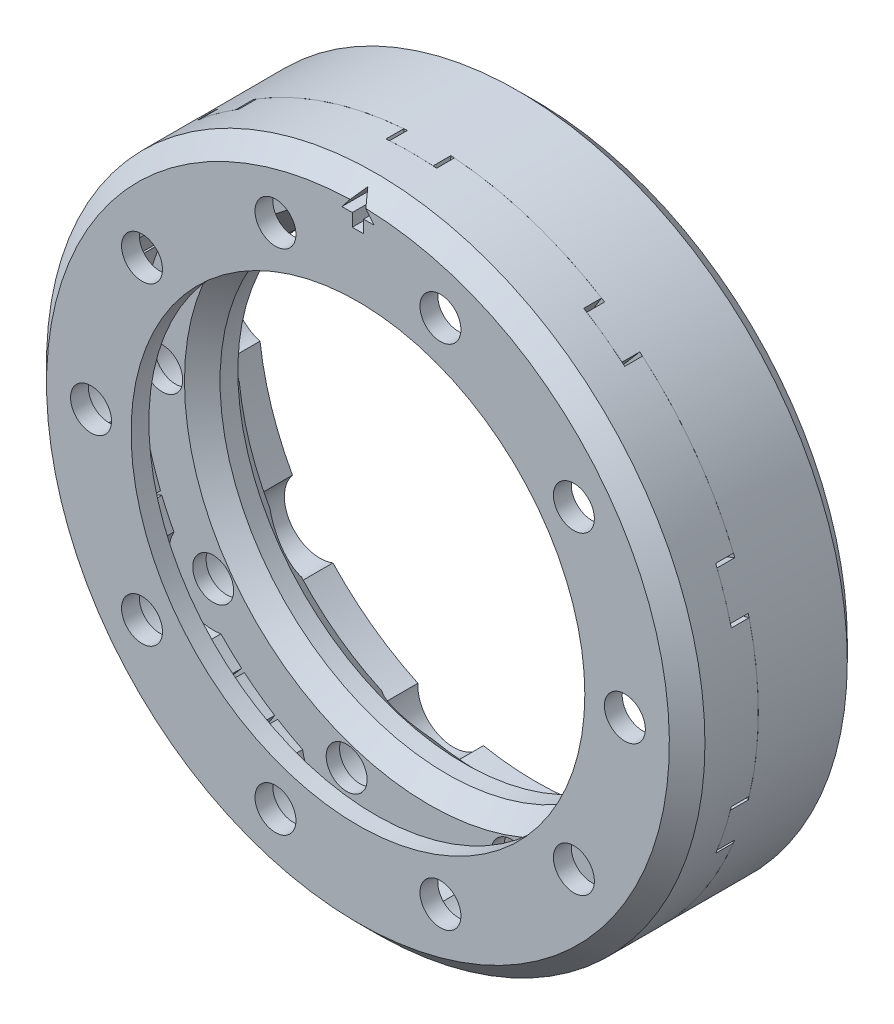
SolidWorks part; units mm, degrees
ref_plane "Front Plane" through (0, 0, 0) normal (0, 0, 1) x (1, 0, 0)
ref_plane "Top Plane" through (0, 0, 0) normal (0, 1, 0) x (1, 0, 0)
ref_plane "Right Plane" through (0, 0, 0) normal (1, 0, 0) x (0, 0, -1)
curve "Curve1"
  spline degree 3 poles (24.0017, -0.2353, 0) (23.9991, 0, 0) (24.0017, 0.2353, 0) (24.0094, 0.4695, 0) (24.022, 0.7014, 0) (24.0393, 0.9301, 0) (24.0607, 1.1546, 0) (24.0858, 1.3743, 0) (24.1142, 1.5885, 0) (24.1451, 1.7968, 0) (24.1782, 1.999, 0) (24.2129, 2.1951, 0) (24.2487, 2.385, 0) (24.2853, 2.5689, 0) (24.3221, 2.747, 0) (24.359, 2.9198, 0) (24.3955, 3.0875, 0) (24.4316, 3.2505, 0) (24.4669, 3.4093, 0) (24.5014, 3.5643, 0) (24.5349, 3.716, 0) (24.5673, 3.8647, 0) (24.5985, 4.0109, 0) (24.6284, 4.1549, 0) (24.6569, 4.2972, 0) (24.6841, 4.438, 0) (24.7098, 4.5776, 0) (24.7339, 4.7164, 0) (24.7564, 4.8545, 0) (24.7773, 4.9923, 0) (24.7964, 5.1299, 0) (24.8137, 5.2675, 0) (24.8292, 5.4052, 0) (24.8427, 5.5433, 0) (24.8542, 5.6817, 0) (24.8635, 5.8205, 0) (24.8707, 5.96, 0) (24.8756, 6.1, 0) (24.8782, 6.2406, 0) (24.8784, 6.3818, 0) (24.8761, 6.5236, 0) (24.8712, 6.666, 0) (24.8637, 6.809, 0) (24.8535, 6.9524, 0) (24.8406, 7.0963, 0) (24.8248, 7.2405, 0) (24.8062, 7.385, 0) (24.7847, 7.5297, 0) (24.7603, 7.6745, 0) (24.7329, 7.8193, 0) (24.7025, 7.964, 0) (24.6691, 8.1084, 0) (24.6328, 8.2524, 0) (24.5934, 8.3959, 0) (24.5511, 8.5389, 0) (24.5059, 8.6811, 0) (24.4577, 8.8224, 0) (24.4066, 8.9627, 0) (24.3527, 9.102, 0) (24.2959, 9.24, 0) (24.2365, 9.3767, 0) (24.1743, 9.5119, 0) (24.1096, 9.6457, 0) (24.0423, 9.7777, 0) (23.9726, 9.908, 0) (23.9006, 10.0365, 0) (23.8262, 10.1632, 0) (23.7497, 10.2878, 0) (23.671, 10.4105, 0) (23.5904, 10.5311, 0) (23.5078, 10.6497, 0) (23.4234, 10.7661, 0) (23.3373, 10.8805, 0) (23.2495, 10.9927, 0) (23.1601, 11.1028, 0) (23.0692, 11.2109, 0) (22.9768, 11.3169, 0) (22.8831, 11.421, 0) (22.7879, 11.5232, 0) (22.6915, 11.6235, 0) (22.5937, 11.7222, 0) (22.4947, 11.8192, 0) (22.3943, 11.9148, 0) (22.2926, 12.0091, 0) (22.1895, 12.1022, 0) (22.0849, 12.1943, 0) (21.9789, 12.2857, 0) (21.8712, 12.3765, 0) (21.7618, 12.4669, 0) (21.6505, 12.5573, 0) (21.5372, 12.6479, 0) (21.4217, 12.739, 0) (21.3038, 12.831, 0) (21.1834, 12.9241, 0) (21.0603, 13.0188, 0) (20.9342, 13.1153, 0) (20.8051, 13.2143, 0) (20.6726, 13.316, 0) (20.5368, 13.421, 0) (20.3976, 13.5296, 0) (20.2548, 13.6424, 0) (20.1086, 13.7598, 0) (19.9591, 13.8822, 0) (19.8065, 14.0101, 0) (19.6512, 14.1438, 0) (19.4936, 14.2834, 0) (19.3342, 14.4293, 0) (19.1738, 14.5814, 0) (19.013, 14.7396, 0) (18.8528, 14.9037, 0) (18.6941, 15.0733, 0) (18.5377, 15.2477, 0) (18.3844, 15.4263, 0) (18.2351, 15.6083, 0) (18.0905, 15.7926, 0) (17.9511, 15.9784, 0) (17.8173, 16.1647, 0) (17.6894, 16.3504, 0) (17.5674, 16.5348, 0) (17.4515, 16.7171, 0) (17.3413, 16.8966, 0) (17.2366, 17.0728, 0) (17.1372, 17.2453, 0) (17.0426, 17.4138, 0) (16.9524, 17.5781, 0) (16.8661, 17.7383, 0) (16.7833, 17.8943, 0) (16.7035, 18.0463, 0) (16.6263, 18.1943, 0) (16.5513, 18.3387, 0) (16.4781, 18.4796, 0) (16.4062, 18.6174, 0) (16.3354, 18.7521, 0) (16.2653, 18.8841, 0) (16.1957, 19.0137, 0) (16.1261, 19.141, 0) (16.0564, 19.2663, 0) (15.9863, 19.3898, 0) (15.9156, 19.5116, 0) (15.8441, 19.6319, 0) (15.7715, 19.7508, 0) (15.6977, 19.8685, 0) (15.6225, 19.9851, 0) (15.5458, 20.1005, 0) (15.4675, 20.2149, 0) (15.3873, 20.3284, 0) (15.3052, 20.4408, 0) (15.2211, 20.5522, 0) (15.1349, 20.6626, 0) (15.0465, 20.772, 0) (14.9558, 20.8803, 0) (14.8629, 20.9874, 0) (14.7676, 21.0934, 0) (14.67, 21.1981, 0) (14.57, 21.3014, 0) (14.4676, 21.4033, 0) (14.3628, 21.5036, 0) (14.2556, 21.6024, 0) (14.1461, 21.6994, 0) (14.0344, 21.7946, 0) (13.9203, 21.8879, 0) (13.8041, 21.9792, 0) (13.6857, 22.0684, 0) (13.5653, 22.1553, 0) (13.4429, 22.24, 0) (13.3186, 22.3223, 0) (13.1925, 22.4021, 0) (13.0647, 22.4794, 0) (12.9354, 22.5541, 0) (12.8046, 22.6261, 0) (12.6724, 22.6954, 0) (12.539, 22.7619, 0) (12.4045, 22.8255, 0) (12.2689, 22.8864, 0) (12.1325, 22.9443, 0) (11.9953, 22.9993, 0) (11.8575, 23.0514, 0) (11.7192, 23.1006, 0) (11.5804, 23.1469, 0) (11.4413, 23.1904, 0) (11.302, 23.2309, 0) (11.1625, 23.2687, 0) (11.023, 23.3036, 0) (10.8836, 23.3358, 0) (10.7442, 23.3654, 0) (10.6049, 23.3923, 0) (10.4658, 23.4166, 0) (10.3269, 23.4385, 0) (10.1882, 23.4579, 0) (10.0496, 23.4751, 0) (9.9112, 23.49, 0) (9.7729, 23.5027, 0) (9.6347, 23.5134, 0) (9.4963, 23.5221, 0) (9.3578, 23.5289, 0) (9.219, 23.5339, 0) (9.0797, 23.5373, 0) (8.9397, 23.5391, 0) (8.7989, 23.5395, 0) (8.6569, 23.5384, 0) (8.5135, 23.5361, 0) (8.3685, 23.5327, 0) (8.2215, 23.5283, 0) (8.0721, 23.5229, 0) (7.92, 23.5169, 0) (7.7648, 23.5102, 0) (7.6062, 23.5032, 0) (7.4436, 23.496, 0) (7.2768, 23.4888, 0) (7.1053, 23.4819, 0) (6.9288, 23.4756, 0) (6.7469, 23.4702, 0) (6.5595, 23.4662, 0) (6.3662, 23.4639, 0) (6.1672, 23.4638, 0) (5.9623, 23.4663, 0) (5.7517, 23.472, 0) (5.5359, 23.4813, 0) (5.3152, 23.4947, 0) (5.0904, 23.5126, 0) (4.8622, 23.5353, 0) (4.6316, 23.5631, 0) (4.3996, 23.5962, 0) (4.1674, 23.6345, 0) (3.9361, 23.6779, 0) (3.7068, 23.7262, 0) (3.4806, 23.7789, 0) (3.2584, 23.8356, 0) (3.041, 23.8957, 0) (2.829, 23.9585, 0) (2.623, 24.0236, 0) (2.4233, 24.0903, 0) (2.2298, 24.158, 0) (2.0428, 24.2262, 0) (1.862, 24.2945, 0) (1.6873, 24.3624, 0) (1.5182, 24.4296, 0) (1.3545, 24.4959, 0) (1.1957, 24.561, 0) (1.0414, 24.6249, 0) (0.8911, 24.6872, 0) (0.7444, 24.7481, 0) (0.6009, 24.8074, 0) (0.4601, 24.8651, 0) (0.3215, 24.9212, 0) (0.1848, 24.9757, 0) (0.0497, 25.0285, 0) (-0.0842, 25.0797, 0) (-0.2173, 25.1292, 0) (-0.3497, 25.1771, 0) (-0.4819, 25.2233, 0) (-0.6139, 25.2678, 0) (-0.7461, 25.3105, 0) (-0.8786, 25.3514, 0) (-1.0116, 25.3906, 0) (-1.1452, 25.4278, 0) (-1.2795, 25.4632, 0) (-1.4146, 25.4965, 0) (-1.5507, 25.5278, 0) (-1.6877, 25.557, 0) (-1.8257, 25.5839, 0) (-1.9647, 25.6086, 0) (-2.1048, 25.631, 0) (-2.2459, 25.6509, 0) (-2.388, 25.6683, 0) (-2.531, 25.6832, 0) (-2.6749, 25.6954, 0) (-2.8197, 25.705, 0) (-2.9653, 25.7117, 0) (-3.1115, 25.7157, 0) (-3.2584, 25.7168, 0) (-3.4057, 25.7149, 0) (-3.5534, 25.7101, 0) (-3.7014, 25.7023, 0) (-3.8496, 25.6916, 0) (-3.9978, 25.6778, 0) (-4.1459, 25.6609, 0) (-4.2938, 25.641, 0) (-4.4413, 25.6181, 0) (-4.5884, 25.5922, 0) (-4.7349, 25.5632, 0) (-4.8807, 25.5313, 0) (-5.0256, 25.4965, 0) (-5.1696, 25.4588, 0) (-5.3125, 25.4183, 0) (-5.4543, 25.375, 0) (-5.5947, 25.3289, 0) (-5.7338, 25.2803, 0) (-5.8714, 25.229, 0) (-6.0075, 25.1753, 0) (-6.1419, 25.1192, 0) (-6.2747, 25.0607, 0) (-6.4058, 25, 0) (-6.5351, 24.9371, 0) (-6.6627, 24.8721, 0) (-6.7884, 24.8051, 0) (-6.9124, 24.7362, 0) (-7.0346, 24.6655, 0) (-7.1551, 24.5929, 0) (-7.2739, 24.5187, 0) (-7.391, 24.4427, 0) (-7.5066, 24.3652, 0) (-7.6207, 24.286, 0) (-7.7335, 24.2053, 0) (-7.8451, 24.1231, 0) (-7.9556, 24.0393, 0) (-8.0652, 23.9539, 0) (-8.1741, 23.8669, 0) (-8.2824, 23.7783, 0) (-8.3906, 23.6881, 0) (-8.4987, 23.596, 0) (-8.607, 23.5021, 0) (-8.7159, 23.4063, 0) (-8.8257, 23.3083, 0) (-8.9367, 23.2082, 0) (-9.0493, 23.1058, 0) (-9.1639, 23.001, 0) (-9.2809, 22.8936, 0) (-9.4008, 22.7836, 0) (-9.524, 22.6709, 0) (-9.6509, 22.5554, 0) (-9.7821, 22.4371, 0) (-9.9179, 22.3161, 0) (-10.0589, 22.1925, 0) (-10.2055, 22.0665, 0) (-10.3579, 21.9385, 0) (-10.5165, 21.8087, 0) (-10.6814, 21.6777, 0) (-10.8527, 21.5461, 0) (-11.0304, 21.4145, 0) (-11.2141, 21.2837, 0) (-11.4036, 21.1544, 0) (-11.5981, 21.0275, 0) (-11.7971, 20.9038, 0) (-11.9996, 20.7839, 0) (-12.2047, 20.6684, 0) (-12.4113, 20.558, 0) (-12.6185, 20.453, 0) (-12.8251, 20.3536, 0) (-13.0303, 20.2598, 0) (-13.2331, 20.1718, 0) (-13.4327, 20.0892, 0) (-13.6286, 20.0119, 0) (-13.8203, 19.9394, 0) (-14.0074, 19.8715, 0) (-14.1898, 19.8076, 0) (-14.3673, 19.7472, 0) (-14.54, 19.6901, 0) (-14.7081, 19.6356, 0) (-14.8716, 19.5834, 0) (-15.0308, 19.5331, 0) (-15.186, 19.4843, 0) (-15.3375, 19.4367, 0) (-15.4856, 19.3898, 0) (-15.6306, 19.3435, 0) (-15.7728, 19.2974, 0) (-15.9125, 19.2513, 0) (-16.0499, 19.2049, 0) (-16.1854, 19.158, 0) (-16.3192, 19.1105, 0) (-16.4514, 19.062, 0) (-16.5823, 19.0124, 0) (-16.7121, 18.9616, 0) (-16.8408, 18.9094, 0) (-16.9686, 18.8556, 0) (-17.0957, 18.8001, 0) (-17.2219, 18.7428, 0) (-17.3475, 18.6835, 0) (-17.4725, 18.6222, 0) (-17.5968, 18.5587, 0) (-17.7205, 18.493, 0) (-17.8436, 18.4249, 0) (-17.966, 18.3545, 0) (-18.0876, 18.2815, 0) (-18.2085, 18.2061, 0) (-18.3286, 18.1281, 0) (-18.4477, 18.0476, 0) (-18.5658, 17.9644, 0) (-18.6829, 17.8787, 0) (-18.7987, 17.7903, 0) (-18.9133, 17.6993, 0) (-19.0265, 17.6057, 0) (-19.1382, 17.5096, 0) (-19.2482, 17.411, 0) (-19.3566, 17.3099, 0) (-19.4632, 17.2064, 0) (-19.5678, 17.1006, 0) (-19.6704, 16.9925, 0) (-19.771, 16.8822, 0) (-19.8692, 16.7698, 0) (-19.9653, 16.6554, 0) (-20.0589, 16.539, 0) (-20.1501, 16.4209, 0) (-20.2387, 16.3011, 0) (-20.3248, 16.1796, 0) (-20.4082, 16.0567, 0) (-20.4889, 15.9324, 0) (-20.5669, 15.8069, 0) (-20.6422, 15.6802, 0) (-20.7147, 15.5525, 0) (-20.7844, 15.4239, 0) (-20.8513, 15.2945, 0) (-20.9154, 15.1643, 0) (-20.9768, 15.0335, 0) (-21.0355, 14.9022, 0) (-21.0914, 14.7705, 0) (-21.1447, 14.6383, 0) (-21.1954, 14.5058, 0) (-21.2435, 14.3731, 0) (-21.2892, 14.2401, 0) (-21.3324, 14.1068, 0) (-21.3733, 13.9734, 0) (-21.412, 13.8396, 0) (-21.4486, 13.7057, 0) (-21.4831, 13.5713, 0) (-21.5157, 13.4366, 0) (-21.5465, 13.3014, 0) (-21.5756, 13.1655, 0) (-21.6031, 13.0289, 0) (-21.6292, 12.8914, 0) (-21.6539, 12.7528, 0) (-21.6776, 12.6128, 0) (-21.7002, 12.4712, 0) (-21.722, 12.3278, 0) (-21.7432, 12.1822, 0) (-21.7639, 12.0342, 0) (-21.7843, 11.8833, 0) (-21.8047, 11.7294, 0) (-21.8253, 11.5719, 0) (-21.8464, 11.4106, 0) (-21.8683, 11.245, 0) (-21.8913, 11.0749, 0) (-21.9158, 10.9, 0) (-21.9421, 10.72, 0) (-21.9707, 10.5347, 0) (-22.0019, 10.344, 0) (-22.0364, 10.1479, 0) (-22.0744, 9.9466, 0) (-22.1166, 9.7402, 0) (-22.1632, 9.5292, 0) (-22.2147, 9.3143, 0) (-22.2714, 9.0959, 0) (-22.3334, 8.8752, 0) (-22.4009, 8.6529, 0) (-22.4738, 8.4302, 0) (-22.5518, 8.2082, 0) (-22.6347, 7.9879, 0) (-22.7221, 7.7705, 0) (-22.8132, 7.5569, 0) (-22.9077, 7.3479, 0) (-23.0046, 7.1442, 0) (-23.1033, 6.9464, 0) (-23.2032, 6.7548, 0) (-23.3035, 6.5697, 0) (-23.4038, 6.391, 0) (-23.5035, 6.2186, 0) (-23.6021, 6.0524, 0) (-23.6993, 5.8921, 0) (-23.7949, 5.7373, 0) (-23.8886, 5.5876, 0) (-23.9803, 5.4425, 0) (-24.0699, 5.3016, 0) (-24.1574, 5.1645, 0) (-24.2429, 5.0306, 0) (-24.3262, 4.8995, 0) (-24.4075, 4.7708, 0) (-24.4868, 4.6441, 0) (-24.5642, 4.519, 0) (-24.6397, 4.3951, 0) (-24.7133, 4.2721, 0) (-24.7852, 4.1497, 0) (-24.8553, 4.0275, 0) (-24.9238, 3.9054, 0) (-24.9905, 3.7831, 0) (-25.0555, 3.6603, 0) (-25.1189, 3.537, 0) (-25.1805, 3.4128, 0) (-25.2404, 3.2877, 0) (-25.2985, 3.1616, 0) (-25.3548, 3.0343, 0) (-25.4093, 2.9058, 0) (-25.4618, 2.7759, 0) (-25.5123, 2.6446, 0) (-25.5608, 2.512, 0) (-25.6071, 2.378, 0) (-25.6512, 2.2425, 0) (-25.693, 2.1056, 0) (-25.7325, 1.9673, 0) (-25.7696, 1.8277, 0) (-25.8041, 1.6867, 0) (-25.836, 1.5446, 0) (-25.8653, 1.4012, 0) (-25.8919, 1.2568, 0) (-25.9156, 1.1114, 0) (-25.9366, 0.9651, 0) (-25.9546, 0.818, 0) (-25.9697, 0.6702, 0) (-25.9819, 0.5219, 0) (-25.991, 0.3731, 0) (-25.9971, 0.224, 0) (-26.0001, 0.0747, 0) (-26.0001, -0.0747, 0) (-25.9971, -0.224, 0) (-25.991, -0.3731, 0) (-25.9819, -0.5219, 0) (-25.9697, -0.6702, 0) (-25.9546, -0.818, 0) (-25.9366, -0.9651, 0) (-25.9156, -1.1114, 0) (-25.8919, -1.2568, 0) (-25.8653, -1.4012, 0) (-25.836, -1.5446, 0) (-25.8041, -1.6867, 0) (-25.7696, -1.8277, 0) (-25.7325, -1.9673, 0) (-25.693, -2.1056, 0) (-25.6512, -2.2425, 0) (-25.6071, -2.378, 0) (-25.5608, -2.512, 0) (-25.5123, -2.6446, 0) (-25.4618, -2.7759, 0) (-25.4093, -2.9058, 0) (-25.3548, -3.0343, 0) (-25.2985, -3.1616, 0) (-25.2404, -3.2877, 0) (-25.1805, -3.4128, 0) (-25.1189, -3.537, 0) (-25.0555, -3.6603, 0) (-24.9905, -3.7831, 0) (-24.9238, -3.9054, 0) (-24.8553, -4.0275, 0) (-24.7852, -4.1497, 0) (-24.7133, -4.2721, 0) (-24.6397, -4.3951, 0) (-24.5642, -4.519, 0) (-24.4868, -4.6441, 0) (-24.4075, -4.7708, 0) (-24.3262, -4.8995, 0) (-24.2429, -5.0306, 0) (-24.1574, -5.1645, 0) (-24.0699, -5.3016, 0) (-23.9803, -5.4425, 0) (-23.8886, -5.5876, 0) (-23.7949, -5.7373, 0) (-23.6993, -5.8921, 0) (-23.6021, -6.0524, 0) (-23.5035, -6.2186, 0) (-23.4038, -6.391, 0) (-23.3035, -6.5697, 0) (-23.2032, -6.7548, 0) (-23.1033, -6.9464, 0) (-23.0046, -7.1442, 0) (-22.9077, -7.3479, 0) (-22.8132, -7.5569, 0) (-22.7221, -7.7705, 0) (-22.6347, -7.9879, 0) (-22.5518, -8.2082, 0) (-22.4738, -8.4302, 0) (-22.4009, -8.6529, 0) (-22.3334, -8.8752, 0) (-22.2714, -9.0959, 0) (-22.2147, -9.3143, 0) (-22.1632, -9.5292, 0) (-22.1166, -9.7402, 0) (-22.0744, -9.9466, 0) (-22.0364, -10.1479, 0) (-22.0019, -10.344, 0) (-21.9707, -10.5347, 0) (-21.9421, -10.72, 0) (-21.9158, -10.9, 0) (-21.8913, -11.0749, 0) (-21.8683, -11.245, 0) (-21.8464, -11.4106, 0) (-21.8253, -11.5719, 0) (-21.8047, -11.7294, 0) (-21.7843, -11.8833, 0) (-21.7639, -12.0342, 0) (-21.7432, -12.1822, 0) (-21.722, -12.3278, 0) (-21.7002, -12.4712, 0) (-21.6776, -12.6128, 0) (-21.6539, -12.7528, 0) (-21.6292, -12.8914, 0) (-21.6031, -13.0289, 0) (-21.5756, -13.1655, 0) (-21.5465, -13.3014, 0) (-21.5157, -13.4366, 0) (-21.4831, -13.5713, 0) (-21.4486, -13.7057, 0) (-21.412, -13.8396, 0) (-21.3733, -13.9734, 0) (-21.3324, -14.1068, 0) (-21.2892, -14.2401, 0) (-21.2435, -14.3731, 0) (-21.1954, -14.5058, 0) (-21.1447, -14.6383, 0) (-21.0914, -14.7705, 0) (-21.0355, -14.9022, 0) (-20.9768, -15.0335, 0) (-20.9154, -15.1643, 0) (-20.8513, -15.2945, 0) (-20.7844, -15.4239, 0) (-20.7147, -15.5525, 0) (-20.6422, -15.6802, 0) (-20.5669, -15.8069, 0) (-20.4889, -15.9324, 0) (-20.4082, -16.0567, 0) (-20.3248, -16.1796, 0) (-20.2387, -16.3011, 0) (-20.1501, -16.4209, 0) (-20.0589, -16.539, 0) (-19.9653, -16.6554, 0) (-19.8692, -16.7698, 0) (-19.771, -16.8822, 0) (-19.6704, -16.9925, 0) (-19.5678, -17.1006, 0) (-19.4632, -17.2064, 0) (-19.3566, -17.3099, 0) (-19.2482, -17.411, 0) (-19.1382, -17.5096, 0) (-19.0265, -17.6057, 0) (-18.9133, -17.6993, 0) (-18.7987, -17.7903, 0) (-18.6829, -17.8787, 0) (-18.5658, -17.9644, 0) (-18.4477, -18.0476, 0) (-18.3286, -18.1281, 0) (-18.2085, -18.2061, 0) (-18.0876, -18.2815, 0) (-17.966, -18.3545, 0) (-17.8436, -18.4249, 0) (-17.7205, -18.493, 0) (-17.5968, -18.5587, 0) (-17.4725, -18.6222, 0) (-17.3475, -18.6835, 0) (-17.2219, -18.7428, 0) (-17.0957, -18.8001, 0) (-16.9686, -18.8556, 0) (-16.8408, -18.9094, 0) (-16.7121, -18.9616, 0) (-16.5823, -19.0124, 0) (-16.4514, -19.062, 0) (-16.3192, -19.1105, 0) (-16.1854, -19.158, 0) (-16.0499, -19.2049, 0) (-15.9125, -19.2513, 0) (-15.7728, -19.2974, 0) (-15.6306, -19.3435, 0) (-15.4856, -19.3898, 0) (-15.3375, -19.4367, 0) (-15.186, -19.4843, 0) (-15.0308, -19.5331, 0) (-14.8716, -19.5834, 0) (-14.7081, -19.6356, 0) (-14.54, -19.6901, 0) (-14.3673, -19.7472, 0) (-14.1898, -19.8076, 0) (-14.0074, -19.8715, 0) (-13.8203, -19.9394, 0) (-13.6286, -20.0119, 0) (-13.4327, -20.0892, 0) (-13.2331, -20.1718, 0) (-13.0303, -20.2598, 0) (-12.8251, -20.3536, 0) (-12.6185, -20.453, 0) (-12.4113, -20.558, 0) (-12.2047, -20.6684, 0) (-11.9996, -20.7839, 0) (-11.7971, -20.9038, 0) (-11.5981, -21.0275, 0) (-11.4036, -21.1544, 0) (-11.2141, -21.2837, 0) (-11.0304, -21.4145, 0) (-10.8527, -21.5461, 0) (-10.6814, -21.6777, 0) (-10.5165, -21.8087, 0) (-10.3579, -21.9385, 0) (-10.2055, -22.0665, 0) (-10.0589, -22.1925, 0) (-9.9179, -22.3161, 0) (-9.7821, -22.4371, 0) (-9.6509, -22.5554, 0) (-9.524, -22.6709, 0) (-9.4008, -22.7836, 0) (-9.2809, -22.8936, 0) (-9.1639, -23.001, 0) (-9.0493, -23.1058, 0) (-8.9367, -23.2082, 0) (-8.8257, -23.3083, 0) (-8.7159, -23.4063, 0) (-8.607, -23.5021, 0) (-8.4987, -23.596, 0) (-8.3906, -23.6881, 0) (-8.2824, -23.7783, 0) (-8.1741, -23.8669, 0) (-8.0652, -23.9539, 0) (-7.9556, -24.0393, 0) (-7.8451, -24.1231, 0) (-7.7335, -24.2053, 0) (-7.6207, -24.286, 0) (-7.5066, -24.3652, 0) (-7.391, -24.4427, 0) (-7.2739, -24.5187, 0) (-7.1551, -24.5929, 0) (-7.0346, -24.6655, 0) (-6.9124, -24.7362, 0) (-6.7884, -24.8051, 0) (-6.6627, -24.8721, 0) (-6.5351, -24.9371, 0) (-6.4058, -25, 0) (-6.2747, -25.0607, 0) (-6.1419, -25.1192, 0) (-6.0075, -25.1753, 0) (-5.8714, -25.229, 0) (-5.7338, -25.2803, 0) (-5.5947, -25.3289, 0) (-5.4543, -25.375, 0) (-5.3125, -25.4183, 0) (-5.1696, -25.4588, 0) (-5.0256, -25.4965, 0) (-4.8807, -25.5313, 0) (-4.7349, -25.5632, 0) (-4.5884, -25.5922, 0) (-4.4413, -25.6181, 0) (-4.2938, -25.641, 0) (-4.1459, -25.6609, 0) (-3.9978, -25.6778, 0) (-3.8496, -25.6916, 0) (-3.7014, -25.7023, 0) (-3.5534, -25.7101, 0) (-3.4057, -25.7149, 0) (-3.2584, -25.7168, 0) (-3.1115, -25.7157, 0) (-2.9653, -25.7117, 0) (-2.8197, -25.705, 0) (-2.6749, -25.6954, 0) (-2.531, -25.6832, 0) (-2.388, -25.6683, 0) (-2.2459, -25.6509, 0) (-2.1048, -25.631, 0) (-1.9647, -25.6086, 0) (-1.8257, -25.5839, 0) (-1.6877, -25.557, 0) (-1.5507, -25.5278, 0) (-1.4146, -25.4965, 0) (-1.2795, -25.4632, 0) (-1.1452, -25.4278, 0) (-1.0116, -25.3906, 0) (-0.8786, -25.3514, 0) (-0.7461, -25.3105, 0) (-0.6139, -25.2678, 0) (-0.4819, -25.2233, 0) (-0.3497, -25.1771, 0) (-0.2173, -25.1292, 0) (-0.0842, -25.0797, 0) (0.0497, -25.0285, 0) (0.1848, -24.9757, 0) (0.3215, -24.9212, 0) (0.4601, -24.8651, 0) (0.6009, -24.8074, 0) (0.7444, -24.7481, 0) (0.8911, -24.6872, 0) (1.0414, -24.6249, 0) (1.1957, -24.561, 0) (1.3545, -24.4959, 0) (1.5182, -24.4296, 0) (1.6873, -24.3624, 0) (1.862, -24.2945, 0) (2.0428, -24.2262, 0) (2.2298, -24.158, 0) (2.4233, -24.0903, 0) (2.623, -24.0236, 0) (2.829, -23.9585, 0) (3.041, -23.8957, 0) (3.2584, -23.8356, 0) (3.4806, -23.7789, 0) (3.7068, -23.7262, 0) (3.9361, -23.6779, 0) (4.1674, -23.6345, 0) (4.3996, -23.5962, 0) (4.6316, -23.5631, 0) (4.8622, -23.5353, 0) (5.0904, -23.5126, 0) (5.3152, -23.4947, 0) (5.5359, -23.4813, 0) (5.7517, -23.472, 0) (5.9623, -23.4663, 0) (6.1672, -23.4638, 0) (6.3662, -23.4639, 0) (6.5595, -23.4662, 0) (6.7469, -23.4702, 0) (6.9288, -23.4756, 0) (7.1053, -23.4819, 0) (7.2768, -23.4888, 0) (7.4436, -23.496, 0) (7.6062, -23.5032, 0) (7.7648, -23.5102, 0) (7.92, -23.5169, 0) (8.0721, -23.5229, 0) (8.2215, -23.5283, 0) (8.3685, -23.5327, 0) (8.5135, -23.5361, 0) (8.6569, -23.5384, 0) (8.7989, -23.5395, 0) (8.9397, -23.5391, 0) (9.0797, -23.5373, 0) (9.219, -23.5339, 0) (9.3578, -23.5289, 0) (9.4963, -23.5221, 0) (9.6347, -23.5134, 0) (9.7729, -23.5027, 0) (9.9112, -23.49, 0) (10.0496, -23.4751, 0) (10.1882, -23.4579, 0) (10.3269, -23.4385, 0) (10.4658, -23.4166, 0) (10.6049, -23.3923, 0) (10.7442, -23.3654, 0) (10.8836, -23.3358, 0) (11.023, -23.3036, 0) (11.1625, -23.2687, 0) (11.302, -23.2309, 0) (11.4413, -23.1904, 0) (11.5804, -23.1469, 0) (11.7192, -23.1006, 0) (11.8575, -23.0514, 0) (11.9953, -22.9993, 0) (12.1325, -22.9443, 0) (12.2689, -22.8864, 0) (12.4045, -22.8255, 0) (12.539, -22.7619, 0) (12.6724, -22.6954, 0) (12.8046, -22.6261, 0) (12.9354, -22.5541, 0) (13.0647, -22.4794, 0) (13.1925, -22.4021, 0) (13.3186, -22.3223, 0) (13.4429, -22.24, 0) (13.5653, -22.1553, 0) (13.6857, -22.0684, 0) (13.8041, -21.9792, 0) (13.9203, -21.8879, 0) (14.0344, -21.7946, 0) (14.1461, -21.6994, 0) (14.2556, -21.6024, 0) (14.3628, -21.5036, 0) (14.4676, -21.4033, 0) (14.57, -21.3014, 0) (14.67, -21.1981, 0) (14.7676, -21.0934, 0) (14.8629, -20.9874, 0) (14.9558, -20.8803, 0) (15.0465, -20.772, 0) (15.1349, -20.6626, 0) (15.2211, -20.5522, 0) (15.3052, -20.4408, 0) (15.3873, -20.3284, 0) (15.4675, -20.2149, 0) (15.5458, -20.1005, 0) (15.6225, -19.9851, 0) (15.6977, -19.8685, 0) (15.7715, -19.7508, 0) (15.8441, -19.6319, 0) (15.9156, -19.5116, 0) (15.9863, -19.3898, 0) (16.0564, -19.2663, 0) (16.1261, -19.141, 0) (16.1957, -19.0137, 0) (16.2653, -18.8841, 0) (16.3354, -18.7521, 0) (16.4062, -18.6174, 0) (16.4781, -18.4796, 0) (16.5513, -18.3387, 0) (16.6263, -18.1943, 0) (16.7035, -18.0463, 0) (16.7833, -17.8943, 0) (16.8661, -17.7383, 0) (16.9524, -17.5781, 0) (17.0426, -17.4138, 0) (17.1372, -17.2453, 0) (17.2366, -17.0728, 0) (17.3413, -16.8966, 0) (17.4515, -16.7171, 0) (17.5674, -16.5348, 0) (17.6894, -16.3504, 0) (17.8173, -16.1647, 0) (17.9511, -15.9784, 0) (18.0905, -15.7926, 0) (18.2351, -15.6083, 0) (18.3844, -15.4263, 0) (18.5377, -15.2477, 0) (18.6941, -15.0733, 0) (18.8528, -14.9037, 0) (19.013, -14.7396, 0) (19.1738, -14.5814, 0) (19.3342, -14.4293, 0) (19.4936, -14.2834, 0) (19.6512, -14.1438, 0) (19.8065, -14.0101, 0) (19.9591, -13.8822, 0) (20.1086, -13.7598, 0) (20.2548, -13.6424, 0) (20.3976, -13.5296, 0) (20.5368, -13.421, 0) (20.6726, -13.316, 0) (20.8051, -13.2143, 0) (20.9342, -13.1153, 0) (21.0603, -13.0188, 0) (21.1834, -12.9241, 0) (21.3038, -12.831, 0) (21.4217, -12.739, 0) (21.5372, -12.6479, 0) (21.6505, -12.5573, 0) (21.7618, -12.4669, 0) (21.8712, -12.3765, 0) (21.9789, -12.2857, 0) (22.0849, -12.1943, 0) (22.1895, -12.1022, 0) (22.2926, -12.0091, 0) (22.3943, -11.9148, 0) (22.4947, -11.8192, 0) (22.5937, -11.7222, 0) (22.6915, -11.6235, 0) (22.7879, -11.5232, 0) (22.8831, -11.421, 0) (22.9768, -11.3169, 0) (23.0692, -11.2109, 0) (23.1601, -11.1028, 0) (23.2495, -10.9927, 0) (23.3373, -10.8805, 0) (23.4234, -10.7661, 0) (23.5078, -10.6497, 0) (23.5904, -10.5311, 0) (23.671, -10.4105, 0) (23.7497, -10.2878, 0) (23.8262, -10.1632, 0) (23.9006, -10.0365, 0) (23.9726, -9.908, 0) (24.0423, -9.7777, 0) (24.1096, -9.6457, 0) (24.1743, -9.5119, 0) (24.2365, -9.3767, 0) (24.2959, -9.24, 0) (24.3527, -9.102, 0) (24.4066, -8.9627, 0) (24.4577, -8.8224, 0) (24.5059, -8.6811, 0) (24.5511, -8.5389, 0) (24.5934, -8.3959, 0) (24.6328, -8.2524, 0) (24.6691, -8.1084, 0) (24.7025, -7.964, 0) (24.7329, -7.8193, 0) (24.7603, -7.6745, 0) (24.7847, -7.5297, 0) (24.8062, -7.385, 0) (24.8248, -7.2405, 0) (24.8406, -7.0963, 0) (24.8535, -6.9524, 0) (24.8637, -6.809, 0) (24.8712, -6.666, 0) (24.8761, -6.5236, 0) (24.8784, -6.3818, 0) (24.8782, -6.2406, 0) (24.8756, -6.1, 0) (24.8707, -5.96, 0) (24.8635, -5.8205, 0) (24.8542, -5.6817, 0) (24.8427, -5.5433, 0) (24.8292, -5.4052, 0) (24.8137, -5.2675, 0) (24.7964, -5.1299, 0) (24.7773, -4.9923, 0) (24.7564, -4.8545, 0) (24.7339, -4.7164, 0) (24.7098, -4.5776, 0) (24.6841, -4.438, 0) (24.6569, -4.2972, 0) (24.6284, -4.1549, 0) (24.5985, -4.0109, 0) (24.5673, -3.8647, 0) (24.5349, -3.716, 0) (24.5014, -3.5643, 0) (24.4669, -3.4093, 0) (24.4316, -3.2505, 0) (24.3955, -3.0875, 0) (24.359, -2.9198, 0) (24.3221, -2.747, 0) (24.2853, -2.5689, 0) (24.2487, -2.385, 0) (24.2129, -2.1951, 0) (24.1782, -1.999, 0) (24.1451, -1.7968, 0) (24.1142, -1.5885, 0) (24.0858, -1.3743, 0) (24.0607, -1.1546, 0) (24.0393, -0.9301, 0) (24.022, -0.7014, 0) (24.0094, -0.4695, 0) (24.0017, -0.2353, 0) (23.9991, 0, 0) (24.0017, 0.2353, 0) knots -0.004329 -0.002897 -0.001452 0 0.001452 0.002897 0.004329 0.005743 0.007134 0.008497 0.009828 0.011126 0.012389 0.013615 0.014805 0.015959 0.017079 0.018167 0.019223 0.020251 0.021252 0.02223 0.023185 0.024122 0.025042 0.025947 0.02684 0.027723 0.028597 0.029464 0.030326 0.031183 0.032039 0.032892 0.033746 0.0346 0.035455 0.036312 0.037172 0.038035 0.038901 0.03977 0.040644 0.041521 0.042403 0.043289 0.044179 0.045072 0.04597 0.046871 0.047776 0.048683 0.049594 0.050506 0.051421 0.052338 0.053256 0.054176 0.055096 0.056016 0.056935 0.057855 0.058773 0.05969 0.060605 0.061518 0.062428 0.063336 0.06424 0.065141 0.066039 0.066932 0.067822 0.068708 0.06959 0.070467 0.071341 0.072211 0.073077 0.073939 0.074799 0.075656 0.076511 0.077365 0.078219 0.079073 0.079928 0.080786 0.081647 0.082514 0.083388 0.084271 0.085164 0.086069 0.086989 0.087926 0.088882 0.089859 0.09086 0.091888 0.092944 0.094032 0.095152 0.096306 0.097496 0.098723 0.099985 0.101283 0.102614 0.103977 0.105368 0.106782 0.108214 0.109659 0.111111 0.112563 0.114008 0.11544 0.116855 0.118245 0.119608 0.120939 0.122237 0.1235 0.124726 0.125916 0.12707 0.12819 0.129278 0.130334 0.131362 0.132363 0.133341 0.134297 0.135233 0.136153 0.137059 0.137952 0.138834 0.139708 0.140575 0.141437 0.142294 0.14315 0.144004 0.144857 0.145711 0.146566 0.147423 0.148283 0.149146 0.150012 0.150881 0.151755 0.152633 0.153514 0.1544 0.15529 0.156183 0.157081 0.157982 0.158887 0.159794 0.160705 0.161617 0.162533 0.163449 0.164368 0.165287 0.166207 0.167127 0.168047 0.168966 0.169884 0.170801 0.171716 0.172629 0.173539 0.174447 0.175351 0.176252 0.17715 0.178044 0.178933 0.179819 0.180701 0.181578 0.182452 0.183322 0.184188 0.18505 0.18591 0.186767 0.187622 0.188476 0.18933 0.190184 0.191039 0.191897 0.192758 0.193625 0.194499 0.195382 0.196275 0.19718 0.1981 0.199037 0.199993 0.20097 0.201971 0.202999 0.204056 0.205143 0.206263 0.207417 0.208607 0.209834 0.211096 0.212394 0.213725 0.215088 0.216479 0.217893 0.219325 0.220771 0.222222 0.223674 0.225119 0.226552 0.227966 0.229356 0.230719 0.232051 0.233348 0.234611 0.235837 0.237027 0.238181 0.239302 0.240389 0.241445 0.242473 0.243474 0.244452 0.245408 0.246344 0.247264 0.24817 0.249063 0.249945 0.250819 0.251686 0.252548 0.253406 0.254261 0.255115 0.255968 0.256822 0.257677 0.258534 0.259394 0.260257 0.261123 0.261993 0.262866 0.263744 0.264625 0.265511 0.266401 0.267295 0.268192 0.269093 0.269998 0.270905 0.271816 0.272729 0.273644 0.27456 0.275479 0.276398 0.277318 0.278238 0.279158 0.280077 0.280995 0.281912 0.282827 0.28374 0.28465 0.285558 0.286462 0.287363 0.288261 0.289155 0.290044 0.29093 0.291812 0.292689 0.293563 0.294433 0.295299 0.296161 0.297021 0.297878 0.298734 0.299587 0.300441 0.301295 0.30215 0.303008 0.30387 0.304737 0.30561 0.306493 0.307386 0.308291 0.309211 0.310148 0.311104 0.312081 0.313083 0.31411 0.315167 0.316254 0.317374 0.318529 0.319719 0.320945 0.322207 0.323505 0.324837 0.326199 0.32759 0.329004 0.330437 0.331882 0.333333 0.334785 0.33623 0.337663 0.339077 0.340467 0.34183 0.343162 0.344459 0.345722 0.346948 0.348138 0.349293 0.350413 0.3515 0.352556 0.353584 0.354585 0.355563 0.356519 0.357455 0.358375 0.359281 0.360174 0.361056 0.36193 0.362797 0.363659 0.364517 0.365372 0.366226 0.367079 0.367933 0.368788 0.369646 0.370505 0.371368 0.372234 0.373104 0.373977 0.374855 0.375736 0.376622 0.377512 0.378406 0.379303 0.380204 0.381109 0.382016 0.382927 0.38384 0.384755 0.385672 0.38659 0.387509 0.388429 0.389349 0.390269 0.391188 0.392106 0.393023 0.393938 0.394851 0.395761 0.396669 0.397573 0.398475 0.399372 0.400266 0.401156 0.402041 0.402923 0.403801 0.404674 0.405544 0.40641 0.407273 0.408132 0.408989 0.409845 0.410699 0.411552 0.412406 0.413261 0.414119 0.414981 0.415848 0.416722 0.417604 0.418497 0.419402 0.420322 0.421259 0.422215 0.423192 0.424194 0.425221 0.426278 0.427365 0.428485 0.42964 0.43083 0.432056 0.433318 0.434616 0.435948 0.43731 0.438701 0.440115 0.441548 0.442993 0.444444 0.445896 0.447341 0.448774 0.450188 0.451578 0.452941 0.454273 0.455571 0.456833 0.458059 0.459249 0.460404 0.461524 0.462611 0.463667 0.464695 0.465697 0.466674 0.46763 0.468567 0.469487 0.470392 0.471285 0.472167 0.473041 0.473908 0.47477 0.475628 0.476483 0.477337 0.47819 0.479044 0.479899 0.480757 0.481616 0.482479 0.483345 0.484215 0.485088 0.485966 0.486848 0.487733 0.488623 0.489517 0.490414 0.491315 0.49222 0.493128 0.494038 0.494951 0.495866 0.496783 0.497701 0.49862 0.49954 0.50046 0.50138 0.502299 0.503217 0.504134 0.505049 0.505962 0.506872 0.50778 0.508685 0.509586 0.510483 0.511377 0.512267 0.513152 0.514034 0.514912 0.515785 0.516655 0.517521 0.518384 0.519243 0.520101 0.520956 0.52181 0.522663 0.523517 0.524372 0.52523 0.526092 0.526959 0.527833 0.528715 0.529608 0.530513 0.531433 0.53237 0.533326 0.534303 0.535305 0.536333 0.537389 0.538476 0.539596 0.540751 0.541941 0.543167 0.544429 0.545727 0.547059 0.548422 0.549812 0.551226 0.552659 0.554104 0.555556 0.557007 0.558452 0.559885 0.561299 0.56269 0.564052 0.565384 0.566682 0.567944 0.56917 0.57036 0.571515 0.572635 0.573722 0.574779 0.575806 0.576808 0.577785 0.578741 0.579678 0.580598 0.581503 0.582396 0.583278 0.584152 0.585019 0.585881 0.586739 0.587594 0.588448 0.589301 0.590155 0.591011 0.591868 0.592727 0.59359 0.594456 0.595326 0.596199 0.597077 0.597959 0.598844 0.599734 0.600628 0.601525 0.602427 0.603331 0.604239 0.605149 0.606062 0.606977 0.607894 0.608812 0.609731 0.610651 0.611571 0.612491 0.61341 0.614328 0.615245 0.61616 0.617073 0.617984 0.618891 0.619796 0.620697 0.621594 0.622488 0.623378 0.624264 0.625145 0.626023 0.626896 0.627766 0.628632 0.629495 0.630354 0.631212 0.632067 0.632921 0.633774 0.634628 0.635483 0.636341 0.637203 0.63807 0.638944 0.639826 0.640719 0.641625 0.642545 0.643481 0.644437 0.645415 0.646416 0.647444 0.6485 0.649587 0.650707 0.651862 0.653052 0.654278 0.655541 0.656838 0.65817 0.659533 0.660923 0.662337 0.66377 0.665215 0.666667 0.668118 0.669563 0.670996 0.67241 0.673801 0.675163 0.676495 0.677793 0.679055 0.680281 0.681471 0.682626 0.683746 0.684833 0.68589 0.686917 0.687919 0.688896 0.689852 0.690789 0.691709 0.692614 0.693507 0.69439 0.695263 0.69613 0.696992 0.69785 0.698705 0.699559 0.700413 0.701266 0.702122 0.702979 0.703839 0.704701 0.705567 0.706437 0.707311 0.708188 0.70907 0.709956 0.710845 0.711739 0.712637 0.713538 0.714442 0.71535 0.71626 0.717173 0.718088 0.719005 0.719923 0.720842 0.721762 0.722682 0.723602 0.724521 0.72544 0.726356 0.727271 0.728184 0.729095 0.730002 0.730907 0.731808 0.732705 0.733599 0.734489 0.735375 0.736256 0.737134 0.738007 0.738877 0.739743 0.740606 0.741466 0.742323 0.743178 0.744032 0.744885 0.745739 0.746594 0.747452 0.748314 0.749181 0.750055 0.750937 0.75183 0.752736 0.753656 0.754592 0.755548 0.756526 0.757527 0.758555 0.759611 0.760698 0.761819 0.762973 0.764163 0.765389 0.766652 0.767949 0.769281 0.770644 0.772034 0.773448 0.774881 0.776326 0.777778 0.779229 0.780675 0.782107 0.783521 0.784912 0.786275 0.787606 0.788904 0.790166 0.791393 0.792583 0.793737 0.794857 0.795944 0.797001 0.798029 0.79903 0.800007 0.800963 0.8019 0.80282 0.803725 0.804618 0.805501 0.806375 0.807242 0.808103 0.808961 0.809816 0.81067 0.811524 0.812378 0.813233 0.81409 0.81495 0.815812 0.816678 0.817548 0.818422 0.819299 0.820181 0.821067 0.821956 0.82285 0.823748 0.824649 0.825553 0.826461 0.827371 0.828284 0.829199 0.830116 0.831034 0.831953 0.832873 0.833793 0.834713 0.835632 0.836551 0.837467 0.838383 0.839295 0.840206 0.841113 0.842018 0.842919 0.843817 0.84471 0.8456 0.846486 0.847367 0.848245 0.849119 0.849988 0.850854 0.851717 0.852577 0.853434 0.854289 0.855143 0.855996 0.85685 0.857706 0.858563 0.859425 0.860292 0.861166 0.862048 0.862941 0.863847 0.864767 0.865703 0.866659 0.867637 0.868638 0.869666 0.870722 0.87181 0.87293 0.874084 0.875274 0.8765 0.877763 0.879061 0.880392 0.881755 0.883145 0.88456 0.885992 0.887437 0.888889 0.890341 0.891786 0.893218 0.894632 0.896023 0.897386 0.898717 0.900015 0.901277 0.902504 0.903694 0.904848 0.905968 0.907056 0.908112 0.90914 0.910141 0.911118 0.912074 0.913011 0.913931 0.914836 0.915729 0.916612 0.917486 0.918353 0.919214 0.920072 0.920927 0.921781 0.922635 0.923489 0.924344 0.925201 0.926061 0.926923 0.927789 0.928659 0.929533 0.93041 0.931292 0.932178 0.933068 0.933961 0.934859 0.93576 0.936664 0.937572 0.938482 0.939395 0.94031 0.941227 0.942145 0.943065 0.943984 0.944904 0.945824 0.946744 0.947662 0.948579 0.949494 0.950406 0.951317 0.952224 0.953129 0.95403 0.954928 0.955821 0.956711 0.957597 0.958479 0.959356 0.96023 0.961099 0.961965 0.962828 0.963688 0.964545 0.9654 0.966254 0.967108 0.967961 0.968817 0.969674 0.970536 0.971403 0.972277 0.97316 0.974053 0.974958 0.975878 0.976815 0.97777 0.978748 0.979749 0.980777 0.981833 0.982921 0.984041 0.985195 0.986385 0.987611 0.988874 0.990172 0.991503 0.992866 0.994257 0.995671 0.997103 0.998548 1 1.001452 1.002897 1.004329 periodic
sketch "Sketch2" plane through (0, 0, 0) normal (0, 0, 1) x (1, 0, 0)
  circle A0 centre (0, 0) radius 37
  dimension "D1" = 74
extrude "Boss-Extrude1" add sketch "Sketch2" along normal blind 6
sketch "Sketch5" plane through (0, 0, 0) normal (0, 0, 1) x (1, 0, 0)
  circle A0 centre (0, 0) radius 31.25
  circle A1 centre (0, 0) radius 37 construction
  circle A2 centre (0, 0) radius 37
  dimension "D1" = 62.5
extrude "Boss-Extrude2" add sketch "Sketch5" against normal blind 6
sketch "Sketch6" plane through (0, 0, 6) normal (0, 0, 1) x (1, 0, 0)
  circle A0 centre (0, 0) radius 25.5
  circle A1 centre (0, 0) radius 37 construction
  circle A2 centre (0, 0) radius 37
  dimension "D1" = 51
extrude "Boss-Extrude3" add sketch "Sketch6" along normal blind 8
sketch "Sketch7" plane through (0, 0, 14) normal (0, 0, 1) x (1, 0, 0)
  line L0 (-1000, 37) -> (49000, 37) construction
  line L1 (0, -1000) -> (0, 49000) construction
  line L2 (0, 32.3993) -> (0.6403, 32.3993)
  line L3 (0.6403, 32.3993) -> (0.6403, 33.8323)
  line L4 (0.6403, 33.8323) -> (1.8002, 33.8323)
  line L5 (1.8002, 33.8323) -> (0, 36.1112)
  line L6 (0, 36.1112) -> (-1.8002, 33.8323)
  line L7 (-1.8002, 33.8323) -> (-0.6403, 33.8323)
  line L8 (-0.6403, 33.8323) -> (-0.6403, 32.3993)
  line L9 (-0.6403, 32.3993) -> (0, 32.3993)
extrude "Cut-Extrude2" cut sketch "Sketch7" against normal through all
sketch "Sketch9" plane through (0, 0, 14) normal (0, 0, 1) x (1, 0, 0)
  circle A0 centre (30, 0) radius 2.3
  dimension "D1" = 4.6
  dimension "D2" = 30
extrude "Cut-Extrude4" cut sketch "Sketch9" against normal through all
sketch "Sketch12" plane through (0, 0, -6) normal (0, 0, -1) x (-1, 0, 0)
  circle A0 centre (-30, 0) radius 4
  dimension "D1" = 8
extrude "Cut-Extrude10" cut sketch "Sketch12" against normal offset from surface (10.5 mm away) 4.5 up to face at (-1.775, 0, 0) offset beyond the face yes
sketch "Sketch15" plane through (0, 0, 6) normal (0, 0, 1) x (1, 0, 0)
  circle A0 centre (30, 0) radius 5
  dimension "D1" = 10
extrude "Cut-Extrude7" cut sketch "Sketch15" along normal blind 6
sketch "Sketch13" plane through (0, 0, 6) normal (0, 0, 1) x (1, 0, 0)
  circle A0 centre (0, 0) radius 25.5
  dimension "D1" = 51
extrude "Cut-Extrude6" cut sketch "Sketch13" against normal through all
pattern_circular "CirPattern7" count 10 over 360 about axis through (0, 0, 6) along (0, 0, -1) of "Cut-Extrude4", "Cut-Extrude7", "Cut-Extrude10" reverse direction yes
sketch "Sketch16" plane through (0, 0, 6) normal (0, 0, 1) x (1, 0, 0)
  circle A0 centre (0, 0) radius 32.5
  dimension "D1" = 65
extrude "Cut-Extrude8" cut sketch "Sketch16" along normal up to surface (6 mm away) up to face at (30.25, 0, 12)
chamfer "Chamfer2" distance 2 angle 45 2 edges at (25.5, 0, 0) (25.5, 0, 6)
sketch "Sketch22" plane through (0, 0, 6) normal (0, 0, 1) x (1, 0, 0)
  circle A0 centre (0, 0) radius 37
  circle A1 centre (0, 0) radius 37 construction
extrude "Cut-Extrude11" cut sketch "Sketch22" against normal blind 0.001 contours A0
sketch "Sketch23" plane through (0, 0, 6) normal (0, 0, -1) x (-1, 0, 0)
  line L0 (-2.5, -32.4037) -> (-2.8462, -36.8904)
  line L1 (2.5, -32.4037) -> (2.8462, -36.8904)
  line L2 (0, -1000) -> (0, 49000) construction
  line L3 (-5.6923, -36.6708) -> (0, -37.11) construction
  circle A0 centre (0, 0) radius 37 construction
  arc A1 (-2.8462, -36.8904) -> (2.8462, -36.8904) centre (0, 0) ccw
  arc A2 (-5.6704, -32.0015) -> (5.6704, -32.0015) centre (0, 0) ccw construction
  arc A3 (-2.5, -32.4037) -> (2.5, -32.4037) centre (0, 0) ccw
  point P9 (0.9271, -37.4931)
  point P14 (0.5268, -37.7381)
  point P15 (-8.8414, -36.739)
  point P16 (-5.931, -36.6524)
  point P17 (0, -37.11)
  dimension "D1" = 5
extrude "Cut-Extrude12" cut sketch "Sketch23" against normal blind 2
pattern_circular "CirPattern9" count 10 over 360 about axis through (0, 0, 6) along (0, 0, -1) of "Cut-Extrude12"
sketch "Sketch24" plane through (0, 0, 5.999) normal (0, 0, 1) x (1, 0, 0)
  line L0 (-2.4472, -36.919) -> (-2.101, -32.432)
  line L1 (2.4472, -36.919) -> (2.101, -32.432)
  line L2 (2.8462, -36.8904) -> (2.5, -32.4037)
  line L3 (-2.5, -32.4037) -> (-2.8462, -36.8904)
  line L4 (2.8462, -36.8904) -> (2.5, -32.4037) construction
  line L5 (-2.5, -32.4037) -> (-2.8462, -36.8904) construction
  line L6 (0, -1000) -> (0, 49000) construction
  arc A2 (-2.8462, -36.8904) -> (2.8462, -36.8904) centre (0, 0) ccw
  arc A3 (-2.5, -32.4037) -> (2.5, -32.4037) centre (0, 0) ccw
  arc A4 (-2.4472, -36.919) -> (2.4472, -36.919) centre (0, 0) ccw
  arc A5 (-2.101, -32.432) -> (2.101, -32.432) centre (0, 0) ccw
  point P10 (0, 0)
  dimension "D2" = 0.4
  dimension "D1" = 0
extrude "Boss-Extrude4" add sketch "Sketch24" along normal blind 2
pattern_circular "CirPattern10" count 10 over 360 about axis through (0, 0, 6) along (0, 0, -1) of "Boss-Extrude4" reverse direction yes
chamfer "Chamfer3" distance 2 angle 45 1 edges at (37, 0, -6)
chamfer "Chamfer4" distance 2 angle 45 1 edges at (37, 0, 14)
